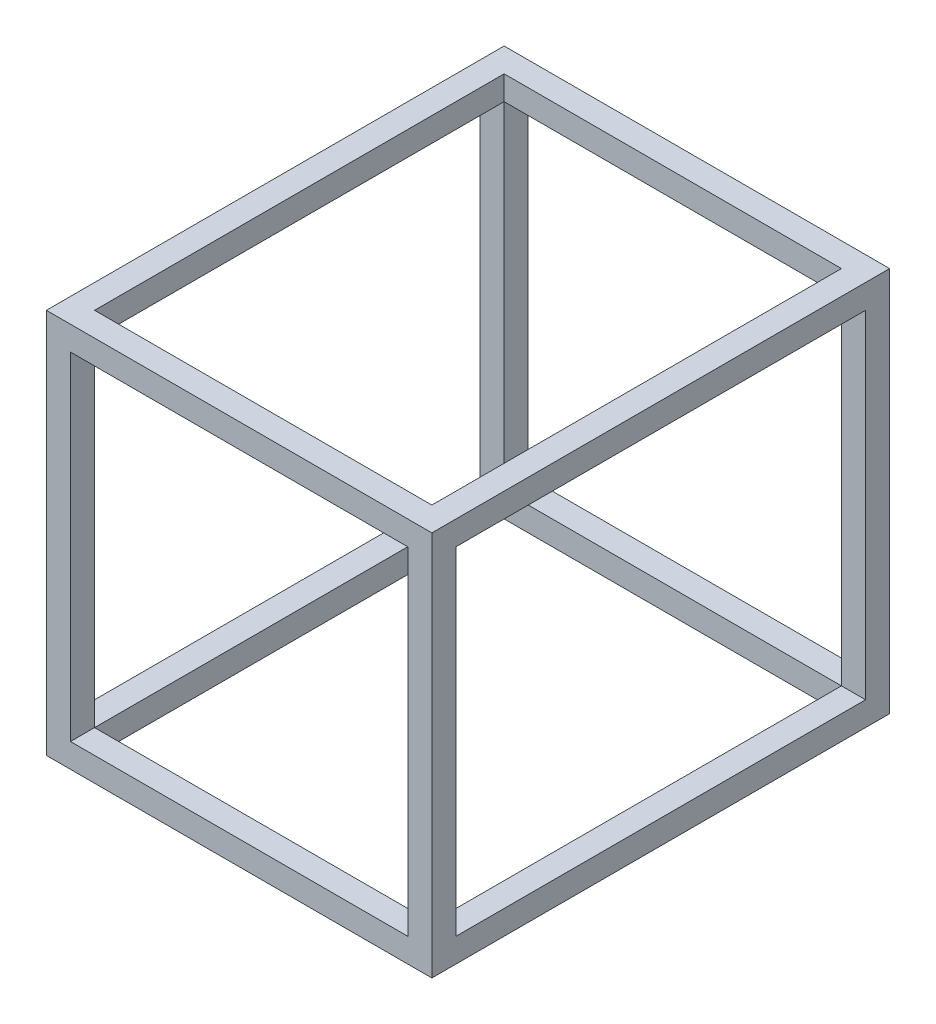
SolidWorks part; units mm, degrees
material "6063-T1"
ref_plane "Front Plane" through (0, 0, 0) normal (1, 0, 0) x (0, 1, 0)
ref_plane "Top Plane" through (0, 0, 0) normal (0, 0, 1) x (0, 1, 0)
ref_plane "Right Plane" through (0, 0, 0) normal (0, 1, 0) x (-1, 0, 0)
sketch "Sketch3" plane through (0, 0, 0) normal (0, 0, 1) x (0, 1, 0)
  line L0 (20, -20) -> (300, -20)
  line L1 (0, 0) -> (320, 0)
  line L2 (0, 0) -> (0, -320)
  line L3 (0, -320) -> (320, -320)
  line L4 (320, 0) -> (320, -320)
  line L5 (300, -20) -> (300, -300)
  line L6 (20, -300) -> (300, -300)
  line L7 (20, -20) -> (20, -300)
  line L8 (300, 0) -> (320, 0)
  line L9 (0, 0) -> (20, 0)
  line L10 (0, 0) -> (0, -20)
  line L11 (0, -20) -> (20, -20)
  line L12 (20, 0) -> (20, -20)
  line L13 (300, 0) -> (300, -20)
  line L14 (320, 0) -> (320, -20)
  line L15 (300, -20) -> (320, -20)
  line L16 (300, -300) -> (320, -300)
  line L17 (300, -300) -> (300, -320)
  line L18 (320, -300) -> (320, -320)
  line L19 (300, -320) -> (320, -320)
  line L20 (0, -300) -> (20, -300)
  line L21 (0, -300) -> (0, -320)
  line L22 (20, -300) -> (20, -320)
  line L23 (0, -320) -> (20, -320)
  line L24 (0, 0) -> (300, 0) construction
  dimension "D1" = 320
  dimension "500" = 320
  dimension "D6" = 300
  dimension "D3" = 20
  dimension "D4" = 2
  dimension "D5" = 2
extrude "Boss-Extrude4" add sketch "Sketch3" along normal blind 20 contours L13 L1 L12 L0 | L2 L20 L7 L11 | L6 L22 L3 L17 | L5 L16 L4 L15 | L12 L1 L2 L11 region at (10, 160, 0) region at (160, 10, 0) region at (10, 10, 0) region at (160, 310, 0) region at (310, 160, 0)
extrude "Boss-Extrude5" add sketch "Sketch3<5>" along normal blind 360 contours L22 L20 L2 L3 | L12 L1 L2 L11 | L13 L15 L4 L1 | L16 L17 L3 L4 region at (10, 10, 0) region at (10, 310, 0) region at (310, 10, 0) region at (310, 310, 0)
sketch "Sketch3<5>" plane through (0, 0, 0) normal (0, 0, 1) x (0, 1, 0) same geometry as "Sketch3"
extrude "Boss-Extrude6" add sketch "Sketch3<7>" along normal blind 20 from surface contours L1 L4 L3 L2 | L0 L5 L6 L7 starting at face at (10, 310, 360)
sketch "Sketch3<7>" plane through (0, 0, 0) normal (0, 0, 1) x (0, 1, 0) same geometry as "Sketch3"
equation "\"extrusion_width\"= 20mm"
equation "\"frame_height\"= 360mm"
equation "\"500@Sketch3\"=\"frame_width\""
equation "\"frame_width\"= 320mm"
equation "\"frame_length\"= 320mm"
equation "\"D1@Sketch3\"=\"frame_length\""
equation "\"D3@Sketch3\"=\"extrusion_width\""
equation "\"D6@Sketch3\"=\"frame_length\"-\"extrusion_width\""
equation "\"D1@Boss-Extrude4\"=\"extrusion_width\""
equation "\"D1@Boss-Extrude5\"=\"frame_height\""
equation "\"bed_radius\"= 200mm"
equation "\"D1@Boss-Extrude6\"=\"extrusion_width\""
